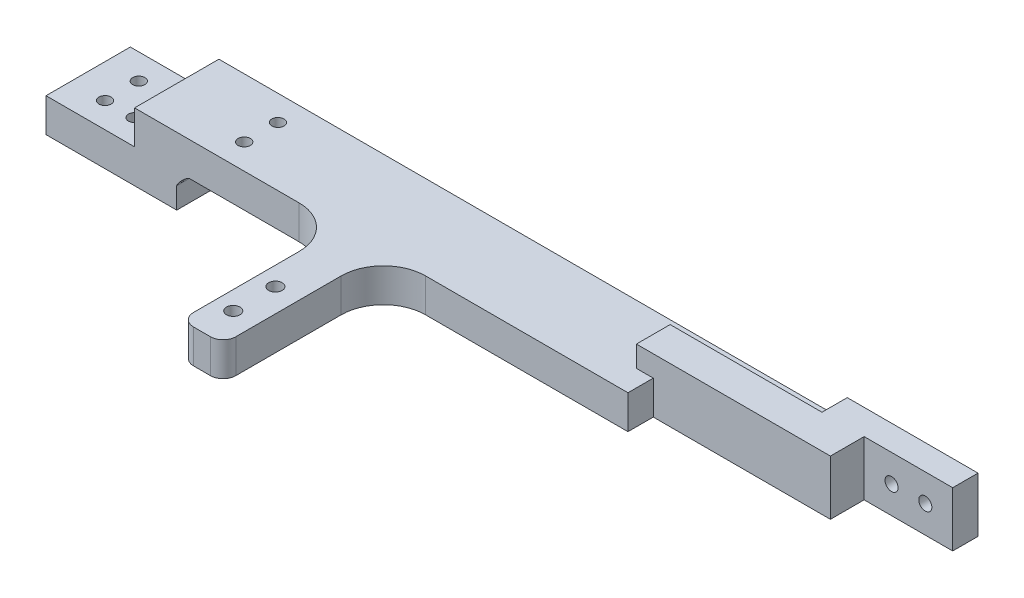
SolidWorks part; units mm, degrees
ref_plane "Front" through (0, 0, 0) normal (0, 0, 1) x (1, 0, 0)
ref_plane "Top" through (0, 0, 0) normal (0, 1, 0) x (1, 0, 0)
ref_plane "Right" through (0, 0, 0) normal (1, 0, 0) x (0, 0, -1)
sketch "Sketch1" plane through (0, 0, 0) normal (0, 1, 0) x (1, 0, 0)
  line L1 (0, 0) -> (300, 0)
  line L2 (0, 0) -> (0, -20)
  line L3 (0, -20) -> (300, -20)
  line L4 (300, 0) -> (300, -20)
  dimension "D1" = 20
  dimension "D2" = 300
extrude "Boss-Extrude1" add sketch "Sketch1" along normal blind 8
sketch "Sketch2" plane through (0, 0, 20) normal (0, 0, 1) x (1, 0, 0)
  line L0 (0, 8) -> (300, 8) construction
  line L1 (0, 0) -> (34, 0)
  line L2 (0, 0) -> (0, 8)
  line L3 (0, 8) -> (34, 8)
  line L4 (34, 0) -> (34, 8)
  line L5 (266, 8) -> (300, 8)
  line L6 (300, 0) -> (300, 8)
  line L7 (266, 0) -> (300, 0)
  line L8 (266, 0) -> (266, 8)
  dimension "D1" = 34
  dimension "D2" = 2
extrude "Boss-Extrude2" add sketch "Sketch2" along normal blind 9
sketch "Sketch3" plane through (0, 0, 0) normal (0, 0, -1) x (-1, 0, 0)
  line L0 (-300, 8) -> (0, 8) construction
  line L1 (0, 0) -> (-34, 0)
  line L2 (0, 0) -> (0, 8)
  line L3 (0, 8) -> (-34, 8)
  line L4 (-34, 0) -> (-34, 8)
  line L5 (-300, 0) -> (-300, 8)
  line L6 (-266, 8) -> (-300, 8)
  line L7 (-266, 0) -> (-266, 8)
  line L8 (-266, 0) -> (-300, 0)
  dimension "D1" = 34
  dimension "D2" = 2
extrude "Boss-Extrude3" add sketch "Sketch3" along normal blind 9
sketch "Sketch4" plane through (0, 8, 0) normal (0, 1, 0) x (1, 0, 0)
  line L0 (0, 9) -> (34, 9) construction
  line L1 (0, 9) -> (0, -29) construction
  circle A0 centre (4, 5) radius 1.45
  circle A1 centre (30, 5) radius 1.45
  circle A2 centre (30, -25) radius 1.45
  circle A3 centre (4, -25) radius 1.45
  circle A4 centre (296, -25) radius 1.45
  circle A5 centre (296, 5) radius 1.45
  circle A6 centre (270, -25) radius 1.45
  circle A7 centre (270, 5) radius 1.45
  dimension "D1" = 2.9
  dimension "D2" = 4
  dimension "D3" = 4
  dimension "D4" = 2
  dimension "D5" = 2
  dimension "D6" = 2
extrude "Cut-Extrude1" cut sketch "Sketch4" against normal through all
sketch "Sketch5" plane through (0, 0, 20) normal (0, 0, 1) x (1, 0, 0)
  line L0 (34, 8) -> (266, 8) construction
  line L1 (266, 0) -> (241, 0)
  line L2 (266, 0) -> (266, 8)
  line L3 (266, 8) -> (241, 8)
  line L4 (241, 0) -> (241, 8)
  dimension "D1" = 25
extrude "Boss-Extrude4" add sketch "Sketch5" along normal blind 17
sketch "Sketch6" plane through (0, 0, 0) normal (0, 0, -1) x (-1, 0, 0)
  line L0 (-266, 0) -> (-34, 0) construction
  line L1 (-266, 8) -> (-241, 8)
  line L2 (-266, 8) -> (-266, 0)
  line L3 (-266, 0) -> (-241, 0)
  line L4 (-241, 8) -> (-241, 0)
  dimension "D1" = 25
extrude "Boss-Extrude5" add sketch "Sketch6" along normal blind 17
sketch "Sketch12" plane through (0, 0, 37) normal (0, 0, 1) x (1, 0, 0)
  line L0 (241, 0) -> (266, 0) construction
  line L1 (241, 8) -> (249, 8)
  line L2 (241, 8) -> (241, 0)
  line L3 (241, 0) -> (249, 0)
  line L4 (249, 8) -> (249, 0)
  dimension "D1" = 8
extrude "Boss-Extrude7" add sketch "Sketch12" along normal blind 17
sketch "Sketch14" plane through (0, 0, 29) normal (0, 0, 1) x (1, 0, 0)
  line L0 (300, 8) -> (266, 8) construction
  line L1 (294.975, 8) -> (275, 8)
  line L2 (294.975, 8) -> (294.975, -5)
  line L3 (294.975, -5) -> (275, -4)
  line L4 (275, 8) -> (275, -4)
  line L7 (266, 8) -> (266, 0) construction
  dimension "D1" = 20
  dimension "D2" = 9
  dimension "D3" = 13
  dimension "D4" = 12
extrude "Boss-Extrude8" add sketch "Sketch14" along normal blind 12
sketch "Sketch15" plane through (294.975, 0, 0) normal (1, 0, 0) x (0, 0, -1)
  line L0 (-41, -5) -> (-41, 8) construction
  line L2 (-41, -5) -> (-29, -5) construction
  circle A0 centre (-35, 0) radius 1.6
  dimension "D1" = 3.2
  dimension "D2" = 6
  dimension "D3" = 5
extrude "Cut-Extrude7" cut sketch "Sketch15" against normal blind 20
sketch "Sketch16" plane through (0, 0, -9) normal (0, 0, -1) x (-1, 0, 0)
  line L0 (-266, 8) -> (-300, 8) construction
  line L1 (-295, 8) -> (-275, 8)
  line L2 (-295, 8) -> (-295, -5)
  line L3 (-295, -5) -> (-275, -5)
  line L4 (-275, 8) -> (-275, -5)
  line L6 (-266, 0) -> (-266, 8) construction
  dimension "D1" = 20
  dimension "D2" = 9
  dimension "D3" = 13
extrude "Boss-Extrude9" add sketch "Sketch16" along normal blind 12
sketch "Sketch17" plane through (295, 0, 0) normal (1, 0, 0) x (0, 0, -1)
  line L0 (21, -5) -> (9, -5) construction
  line L1 (21, 8) -> (21, -5) construction
  circle A0 centre (15, 0) radius 1.6
  dimension "D1" = 3.2
  dimension "D2" = 5
  dimension "D3" = 6
extrude "Cut-Extrude8" cut sketch "Sketch17" against normal blind 20
sketch "Sketch18" plane through (0, 0, -9) normal (0, 0, -1) x (-1, 0, 0)
  line L0 (0, 8) -> (-34, 8) construction
  line L1 (-25, 8) -> (-5, 8)
  line L2 (-25, 8) -> (-25, -5)
  line L3 (-25, -5) -> (-5, -5)
  line L4 (-5, 8) -> (-5, -5)
  line L6 (-34, 8) -> (-34, 0) construction
  dimension "D1" = 20
  dimension "D2" = 9
  dimension "D3" = 13
extrude "Boss-Extrude10" add sketch "Sketch18" along normal blind 12
sketch "Sketch19" plane through (5, 0, 0) normal (-1, 0, 0) x (0, 0, 1)
  line L0 (-21, -5) -> (-21, 8) construction
  line L2 (-21, -5) -> (-9, -5) construction
  circle A0 centre (-15, 0) radius 1.6
  dimension "D1" = 3.2
  dimension "D2" = 6
  dimension "D3" = 5
extrude "Cut-Extrude9" cut sketch "Sketch19" against normal blind 20
sketch "Sketch20" plane through (0, 0, 29) normal (0, 0, 1) x (1, 0, 0)
  line L0 (34, 8) -> (0, 8) construction
  line L1 (5, 8) -> (25, 8)
  line L2 (5, 8) -> (5, -5)
  line L3 (5, -5) -> (25, -5)
  line L4 (25, 8) -> (25, -5)
  line L6 (34, 0) -> (34, 8) construction
  dimension "D1" = 20
  dimension "D2" = 9
  dimension "D3" = 13
extrude "Boss-Extrude11" add sketch "Sketch20" along normal blind 12
sketch "Sketch21" plane through (5, 0, 0) normal (-1, 0, 0) x (0, 0, 1)
  line L0 (41, 8) -> (41, -5) construction
  line L1 (41, -5) -> (29, -5) construction
  circle A0 centre (35, 0) radius 1.6
  dimension "D1" = 3.2
  dimension "D2" = 6
  dimension "D3" = 5
extrude "Cut-Extrude10" cut sketch "Sketch21" against normal blind 20
sketch "Sketch22" plane through (0, 8, 0) normal (0, 1, 0) x (1, 0, 0)
  line L0 (241, 17) -> (241, 0) construction
  line L1 (259, 9) -> (249, 9)
  line L2 (259, 9) -> (259, -29)
  line L3 (259, -29) -> (249, -29)
  line L4 (249, 9) -> (249, -29)
  line L5 (241, 17) -> (266, 17) construction
  line L6 (266, -37) -> (249, -37) construction
  dimension "D1" = 8
  dimension "D2" = 10
  dimension "D3" = 8
  dimension "D4" = 8
extrude "Cut-Extrude11" cut sketch "Sketch22" against normal through all
sketch "Sketch23" plane through (0, 0, 0) normal (0, -1, 0) x (-1, 0, 0)
  line L0 (-259, -29) -> (-259, 9) construction
  line L1 (-259, -19) -> (-267, -19)
  line L2 (-259, -19) -> (-259, -1)
  line L3 (-259, -1) -> (-267, -1)
  line L4 (-267, -19) -> (-267, -1)
  line L5 (-249, -29) -> (-259, -29) construction
  dimension "D1" = 8
  dimension "D2" = 10
  dimension "D3" = 10
extrude "Cut-Extrude12" cut sketch "Sketch23" against normal blind 4
sketch "Sketch24" plane through (259, 0, 0) normal (-1, 0, 0) x (0, 0, 1)
  line L0 (-9, 0) -> (-9, 8)
  line L1 (-9, 8) -> (-1, 8)
  line L2 (29, 8) -> (-9, 8) construction
  line L3 (-1, 8) -> (-9, 0)
  line L4 (29, 0) -> (29, 8)
  line L5 (29, 8) -> (21, 8)
  line L6 (21, 8) -> (29, 0)
  dimension "D1" = 8
  dimension "D2" = 8
extrude "Boss-Extrude12" add sketch "Sketch24" along normal blind 10
sketch "Sketch25" plane through (267, 0, 0) normal (-1, 0, 0) x (0, 0, 1)
  line L0 (19, 0) -> (19, 4)
  line L1 (19, 4) -> (15, 4)
  line L2 (1, 4) -> (19, 4) construction
  line L3 (15, 4) -> (19, 0)
  line L4 (1, 4) -> (5, 4)
  line L5 (5, 4) -> (1, 0)
  line L6 (1, 0) -> (1, 4)
  dimension "D1" = 4
  dimension "D2" = 4
extrude "Boss-Extrude13" add sketch "Sketch25" along normal blind 8
sketch "Sketch26" plane through (0, 8, 0) normal (0, 1, 0) x (1, 0, 0)
  line L0 (249, 1) -> (249, -21) construction
  line L1 (241, -54) -> (249, -54)
  line L2 (241, -54) -> (241, -6)
  line L3 (241, -6) -> (249, -6)
  line L4 (249, -54) -> (249, -6)
  dimension "D1" = 48
extrude "Boss-Extrude14" add sketch "Sketch26" along normal blind 14
sketch "Sketch27" plane through (0, 8, 0) normal (0, 1, 0) x (1, 0, 0)
  line L0 (249, -21) -> (259, -21) construction
  line L1 (249, -37) -> (257, -37)
  line L2 (249, -37) -> (249, -21)
  line L3 (249, -21) -> (257, -21)
  line L4 (257, -37) -> (257, -21)
  dimension "D1" = 8
extrude "Boss-Extrude15" add sketch "Sketch27" along normal blind 14
sketch "Sketch28" plane through (0, 0, 0) normal (0, -1, 0) x (1, 0, 0)
  line L0 (249, -9) -> (249, 29) construction
  line L1 (241, 54) -> (249, 54)
  line L2 (241, 54) -> (241, 14)
  line L3 (241, 14) -> (249, 14)
  line L4 (249, 54) -> (249, 14)
  dimension "D1" = 40
extrude "Cut-Extrude13" cut sketch "Sketch28" against normal blind 14
sketch "Sketch30" plane through (257, 0, 0) normal (1, 0, 0) x (0, 0, -1)
  line L0 (-37, 22) -> (-21, 22) construction
  line L1 (-21, 22) -> (-37, 22)
  line L2 (-21, 22) -> (-21, 8)
  line L3 (-21, 8) -> (-37, 8)
  line L4 (-37, 22) -> (-37, 8)
extrude "Boss-Extrude16" add sketch "Sketch30" along normal blind 9
sketch "Sketch31" plane through (0, 0, 0) normal (0, -1, 0) x (-1, 0, 0)
  line L1 (-249, -37) -> (-266, -37)
  line L2 (-249, -37) -> (-249, -29)
  line L3 (-249, -29) -> (-266, -29)
  line L4 (-266, -37) -> (-266, -29)
extrude "Cut-Extrude14" cut sketch "Sketch31" against normal blind 5
sketch "Sketch32" plane through (266, 0, 0) normal (1, 0, 0) x (0, 0, -1)
  line L0 (-37, 5) -> (-37, 22) construction
  line L1 (-21, 22) -> (-37, 22)
  line L2 (-21, 22) -> (-21, 13)
  line L3 (-21, 13) -> (-37, 13)
  line L4 (-37, 22) -> (-37, 13)
  dimension "D1" = 9
extrude "Cut-Extrude15" cut sketch "Sketch32" against normal blind 9
sketch "Sketch33" plane through (249, 0, 0) normal (-1, 0, 0) x (0, 0, 1)
  line L0 (29, 5) -> (24, 5)
  line L1 (21, 8) -> (29, 0) construction
  line L2 (24, 5) -> (29, 0)
  line L3 (29, 0) -> (29, 5)
extrude "Cut-Extrude16" cut sketch "Sketch33" against normal blind 10
sketch "Sketch34" plane through (0, 0, 29) normal (0, 0, 1) x (1, 0, 0)
  line L1 (266, 5) -> (259, 5)
  line L2 (266, 5) -> (266, 0)
  line L3 (266, 0) -> (259, 0)
  line L4 (259, 5) -> (259, 0)
extrude "Cut-Extrude17" cut sketch "Sketch34" against normal blind 5
sketch "Sketch35" plane through (0, 0, 21) normal (0, 0, -1) x (-1, 0, 0)
  line L0 (-249, 8) -> (-259, 8) construction
  line L1 (-259, 8) -> (-266, 8)
  line L2 (-259, 8) -> (-259, 13)
  line L3 (-259, 13) -> (-266, 13)
  line L4 (-266, 8) -> (-266, 13)
  line L5 (-266, 8) -> (-259, 8) construction
  line L6 (-266, 8) -> (-266, 13) construction
extrude "Boss-Extrude17" add sketch "Sketch35" along normal blind 5
sketch "Sketch36" plane through (0, 22, 0) normal (0, 1, 0) x (1, 0, 0)
  line L0 (241, -54) -> (249, -54) construction
  line L1 (249, -54) -> (249, -37) construction
  circle A0 centre (245, -50) radius 1.7
  circle A1 centre (245, -18) radius 1.7
  dimension "D1" = 3.4
  dimension "D2" = 4
  dimension "D3" = 4
  dimension "D4" = 2
extrude "Cut-Extrude18" cut sketch "Sketch36" against normal through all
sketch "Sketch37" plane through (0, 8, 0) normal (0, 1, 0) x (1, 0, 0)
  line L0 (241, -6) -> (171, -6)
  line L1 (241, -6) -> (241, -14) construction
  line L2 (241, -6) -> (241, -14)
  line L3 (241, -14) -> (241, -20) construction
  line L4 (241, -14) -> (171, -14)
  line L5 (171, -14) -> (171, -6)
  dimension "D1" = 70
extrude "Boss-Extrude18" add sketch "Sketch37" along normal blind 5
sketch "Sketch39" plane through (0, 8, 0) normal (0, 1, 0) x (1, 0, 0)
  line L0 (34, -20) -> (241, -20) construction
  line L1 (241, -14) -> (175, -14)
  line L2 (241, -14) -> (241, -20)
  line L3 (241, -20) -> (175, -20)
  line L4 (175, -14) -> (175, -20)
  dimension "D1" = 66
extrude "Cut-Extrude19" cut sketch "Sketch39" against normal through all
sketch "Sketch40" plane through (0, 8, 0) normal (0, 1, 0) x (1, 0, 0)
  line L1 (5, 9) -> (25, 9)
  line L2 (5, 9) -> (5, 21)
  line L3 (5, 21) -> (25, 21)
  line L4 (25, 9) -> (25, 21)
extrude "Boss-Extrude19" add sketch "Sketch40" along normal blind 10
sketch "Sketch41" plane through (0, 18, 0) normal (0, 1, 0) x (1, 0, 0)
  line L0 (25, 21) -> (5, 21) construction
  line L1 (25, 21) -> (-3, 21)
  line L2 (25, 21) -> (25, 9)
  line L3 (25, 9) -> (-3, 9)
  line L4 (-3, 21) -> (-3, 9)
  line L5 (5, 9) -> (25, 9) construction
  line L6 (25, 9) -> (25, 21) construction
  line L7 (5, 21) -> (5, 9) construction
  dimension "D1" = 28
  dimension "D2" = 20
extrude "Boss-Extrude20" add sketch "Sketch41" along normal blind 5 and the other way blind 5
sketch "Sketch42" plane through (-3, 0, 0) normal (-1, 0, 0) x (0, 0, 1)
  line L0 (-21, 23) -> (-9, 23) construction
  line L1 (-9, 13) -> (-9, 23) construction
  circle A0 centre (-14, 18) radius 1.5
  dimension "D1" = 3
  dimension "D2" = 5
  dimension "D3" = 5
extrude "Cut-Extrude20" cut sketch "Sketch42" against normal blind 15
sketch "Sketch43" plane through (0, 8, 0) normal (0, 1, 0) x (1, 0, 0)
  line L1 (5, -41) -> (25, -41)
  line L2 (5, -41) -> (5, -29)
  line L3 (5, -29) -> (25, -29)
  line L4 (25, -41) -> (25, -29)
extrude "Boss-Extrude21" add sketch "Sketch43" along normal blind 10
sketch "Sketch44" plane through (0, 18, 0) normal (0, 1, 0) x (1, 0, 0)
  line L0 (25, -29) -> (5, -29) construction
  line L1 (-3, -29) -> (25, -29)
  line L2 (-3, -29) -> (-3, -41)
  line L3 (-3, -41) -> (25, -41)
  line L4 (25, -29) -> (25, -41)
  line L5 (5, -41) -> (25, -41) construction
  line L6 (25, -41) -> (25, -29) construction
  line L7 (5, -29) -> (5, -41) construction
  dimension "D1" = 28
  dimension "D2" = 20
extrude "Boss-Extrude22" add sketch "Sketch44" along normal blind 5 and the other way blind 5
sketch "Sketch45" plane through (-3, 0, 0) normal (-1, 0, 0) x (0, 0, 1)
  line L0 (29, 23) -> (41, 23) construction
  line L1 (41, 13) -> (41, 23) construction
  circle A0 centre (36, 18) radius 1.5
  dimension "D1" = 3
  dimension "D2" = 5
  dimension "D3" = 5
extrude "Cut-Extrude21" cut sketch "Sketch45" against normal blind 15
sketch "Sketch46" plane through (0, 8, 0) normal (0, 1, 0) x (1, 0, 0)
  line L1 (295, 9) -> (275, 9)
  line L2 (295, 9) -> (295, 21)
  line L3 (295, 21) -> (275, 21)
  line L4 (275, 9) -> (275, 21)
  line L5 (294.975, -41) -> (275, -41)
  line L6 (294.975, -41) -> (294.975, -29)
  line L7 (294.975, -29) -> (275, -29)
  line L8 (275, -41) -> (275, -29)
extrude "Boss-Extrude23" add sketch "Sketch46" along normal blind 10
sketch "Sketch47" plane through (0, 18, 0) normal (0, 1, 0) x (1, 0, 0)
  line L0 (295, 21) -> (275, 21) construction
  line L1 (275, 21) -> (303, 21)
  line L2 (275, 21) -> (275, 9)
  line L3 (275, 9) -> (303, 9)
  line L4 (303, 21) -> (303, 9)
  line L5 (275, 9) -> (295, 9) construction
  line L6 (294.975, -29) -> (275, -29) construction
  line L7 (274.975, -29) -> (303, -29)
  line L8 (274.975, -29) -> (274.975, -41)
  line L9 (274.975, -41) -> (303, -41)
  line L10 (303, -29) -> (303, -41)
  line L11 (275, -41) -> (294.975, -41) construction
  line L12 (275, 21) -> (275, 9) construction
  line L13 (295, 9) -> (295, 21) construction
  line L14 (275, -29) -> (275, -41) construction
  line L15 (294.975, -41) -> (294.975, -29) construction
  dimension "D1" = 28
  dimension "D2" = 20
  dimension "D3" = 28
  dimension "D4" = 20
extrude "Boss-Extrude24" add sketch "Sketch47" along normal blind 5 and the other way blind 5
sketch "Sketch48" plane through (303, 0, 0) normal (1, 0, 0) x (0, 0, -1)
  line L2 (-41, 13) -> (-41, 23) construction
  line L3 (21, 13) -> (21, 23) construction
  line L4 (9, 23) -> (21, 23) construction
  line L5 (-41, 23) -> (-29, 23) construction
  circle A0 centre (16, 18) radius 1.5
  circle A1 centre (-36, 18) radius 1.5
  dimension "D1" = 3
  dimension "D2" = 3
  dimension "D3" = 5
  dimension "D4" = 5
  dimension "D5" = 5
  dimension "D6" = 5
extrude "Cut-Extrude22" cut sketch "Sketch48" against normal blind 15
fillet "Fillet1" radius 5 4 edges at (294.975, 13, 35) (295, 13, -15) (5, 13, 35) (5, 13, -15)
fillet "Fillet2" radius 2.5 4 edges at (15, 8, -9) (15, 8, 29) (284.9875, 8, 29) (285, 8, -9)
fillet "Fillet3" radius 3 8 edges at (284.9875, -4.5, 41) (284.9875, -4.5, 29) (285, -5, -21) (285, -5, -9) (15, -5, -21) (15, -5, -9) (15, -5, 29) (15, -5, 41)
fillet "Fillet4" radius 3 8 edges at (11, 23, -21) (11, 23, -9) (11, 23, 29) (11, 23, 41) (289, 23, -9) (289, 23, -21) (288.9875, 23, 41) (288.9875, 23, 29)
sketch "Sketch49" plane through (0, 8, 0) normal (0, 1, 0) x (1, 0, 0)
  line L0 (241, 0) -> (34, 0) construction
  line L1 (34, -20) -> (175, -20) construction
  line L2 (0, 9) -> (0, -29) construction
  circle A0 centre (78, -6) radius 1.45
  circle A1 centre (78, -14) radius 1.45
  dimension "D1" = 2.9
  dimension "D2" = 2.9
  dimension "D3" = 6
  dimension "D4" = 6
  dimension "D5" = 78
  dimension "D6" = 78
extrude "Cut-Extrude23" cut sketch "Sketch49" against normal through all
sketch "Sketch50" plane through (-3, 0, 0) normal (-1, 0, 0) x (0, 0, 1)
  line L1 (-34.8128, -21.6618) -> (62.794, -21.6618)
  line L2 (-34.8128, -21.6618) -> (-34.8128, 36.6095)
  line L3 (-34.8128, 36.6095) -> (62.794, 36.6095)
  line L4 (62.794, -21.6618) -> (62.794, 36.6095)
extrude "Cut-Extrude24" cut sketch "Sketch50" against normal blind 40
sketch "Sketch51" plane through (303, 0, 0) normal (1, 0, 0) x (0, 0, -1)
  line L1 (33.5869, 36.8102) -> (-70.4933, 36.8102)
  line L2 (33.5869, 36.8102) -> (33.5869, -31.9678)
  line L3 (33.5869, -31.9678) -> (-70.4933, -31.9678)
  line L4 (-70.4933, 36.8102) -> (-70.4933, -31.9678)
extrude "Cut-Extrude25" cut sketch "Sketch51" against normal blind 65
sketch "Sketch54" plane through (238, 0, 0) normal (1, 0, 0) x (0, 0, -1)
  line L1 (-6, 13) -> (-14, 13)
  line L2 (-6, 13) -> (-6, 0)
  line L3 (-6, 0) -> (-14, 0)
  line L4 (-14, 13) -> (-14, 0)
extrude "Cut-Extrude26" cut sketch "Sketch54" against normal blind 21
sketch "Sketch55" plane through (0, 8, 0) normal (0, 1, 0) x (1, 0, 0)
  line L0 (238, 0) -> (37, 0) construction
  line L1 (238, -6) -> (207, -6)
  line L2 (238, -6) -> (238, 0)
  line L3 (238, 0) -> (207, 0)
  line L4 (207, -6) -> (207, 0)
  dimension "D1" = 31
extrude "Boss-Extrude26" add sketch "Sketch55" along normal blind 5
sketch "Sketch56" plane through (0, 0, 6) normal (0, 0, 1) x (1, 0, 0)
  line L0 (217, 0) -> (217, 13) construction
  circle A0 centre (231.5, 6.5) radius 1.55
  circle A1 centre (223.5, 6.5) radius 1.55
  dimension "D1" = 3.1
  dimension "D2" = 3.1
  dimension "D3" = 8
  dimension "D4" = 6.5
extrude "Cut-Extrude27" cut sketch "Sketch56" against normal through all
sketch "Sketch57" plane through (0, 0, 0) normal (0, -1, 0) x (-1, 0, 0)
  line L0 (-238, 0) -> (-37, 0) construction
  line L1 (-37, -20) -> (-68, -20)
  line L2 (-37, -20) -> (-37, 0)
  line L3 (-37, 0) -> (-68, 0)
  line L4 (-68, -20) -> (-68, 0)
  dimension "D1" = 31
extrude "Boss-Extrude27" add sketch "Sketch57" along normal blind 8
sketch "Sketch58" plane through (0, 8, 0) normal (0, 1, 0) x (1, 0, 0)
  line L0 (37, -20) -> (175, -20) construction
  line L1 (37, 0) -> (58, 0)
  line L2 (37, 0) -> (37, -20)
  line L3 (37, -20) -> (58, -20)
  line L4 (58, 0) -> (58, -20)
  dimension "D1" = 21
extrude "Cut-Extrude28" cut sketch "Sketch58" against normal blind 8
sketch "Sketch59" plane through (0, 0, 0) normal (0, 1, 0) x (1, 0, 0)
  line L1 (58, 0) -> (37, 0) construction
  line L2 (37, -20) -> (58, -20) construction
  line L3 (58, -20) -> (58, 0) construction
  circle A0 centre (52, -6) radius 1.45
  circle A1 centre (45, -6) radius 1.45
  circle A2 centre (45, -14) radius 1.45
  circle A3 centre (52, -14) radius 1.45
  dimension "D2" = 2.9
  dimension "D3" = 2.9
  dimension "D4" = 2.9
  dimension "D1" = 2.9
  dimension "D5" = 6
  dimension "D6" = 6
  dimension "D7" = 6
  dimension "D8" = 6
  dimension "D9" = 7
  dimension "D10" = 7
extrude "Cut-Extrude29" cut sketch "Sketch59" against normal through all
sketch "Sketch60" plane through (0, 0, 20) normal (0, 0, 1) x (1, 0, 0)
  line L0 (68, 0) -> (175, 0) construction
  line L1 (107, 0) -> (117, 0)
  line L2 (107, 0) -> (107, 8)
  line L3 (107, 8) -> (117, 8)
  line L4 (117, 0) -> (117, 8)
  line L5 (58, 8) -> (175, 8) construction
  line L6 (58, 0) -> (58, 8) construction
  dimension "D1" = 10
  dimension "D2" = 49
extrude "Boss-Extrude28" add sketch "Sketch60" along normal blind 38
sketch "Sketch61" plane through (0, 8, 0) normal (0, 1, 0) x (1, 0, 0)
  line L0 (107, -58) -> (107, -20) construction
  line L1 (58, -20) -> (107, -20) construction
  circle A0 centre (111.4, -50) radius 1.6
  circle A1 centre (111.4, -40) radius 1.6
  dimension "D1" = 3.2
  dimension "D2" = 3.2
  dimension "D3" = 10
  dimension "D4" = 4.4
  dimension "D5" = 4.4
  dimension "D6" = 20
extrude "Cut-Extrude30" cut sketch "Sketch61" against normal through all
fillet "Fillet5" radius 10 2 edges at (107, 4, 20) (117, 4, 20)
fillet "Fillet6" radius 3 1 edges at (68, 0, 10) conic rho 0.15
fillet "Fillet7" radius 3 2 edges at (117, 4, 58) (107, 4, 58)
